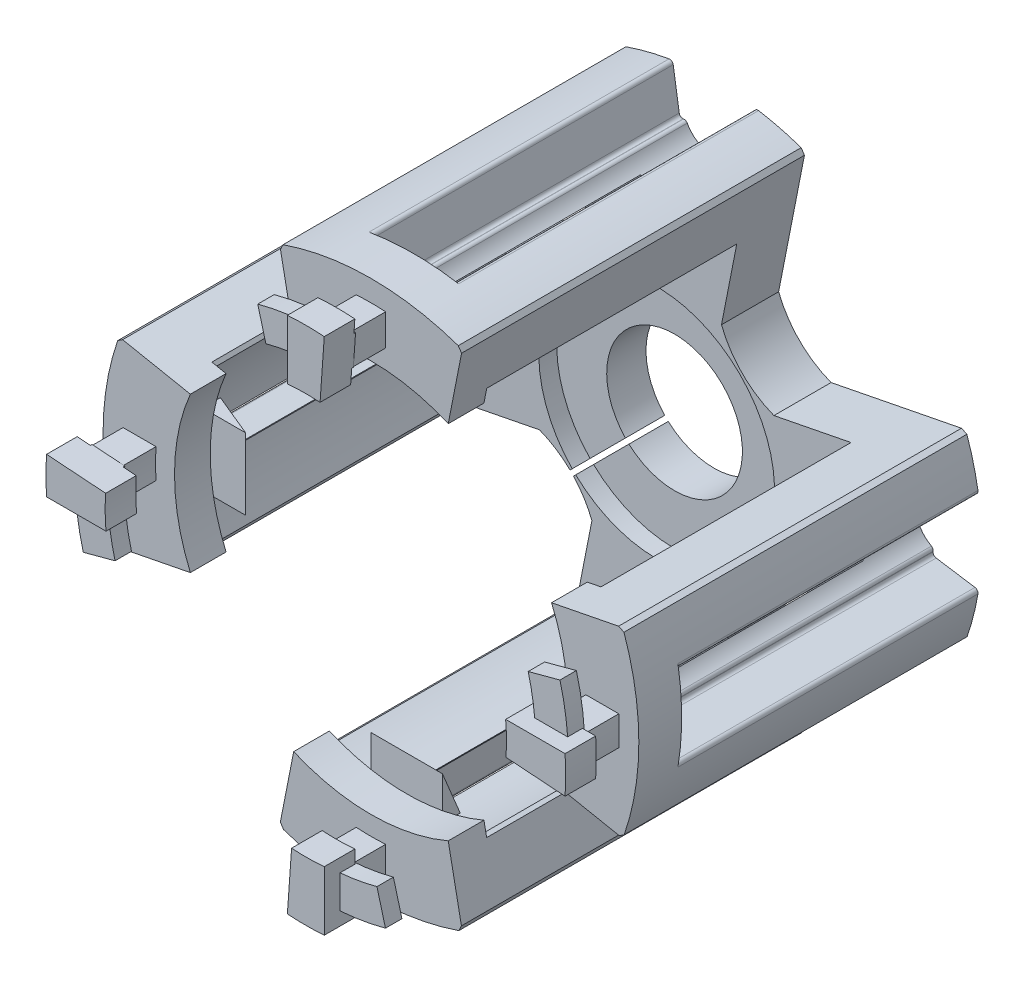
SolidWorks part; units mm, degrees
ref_plane "Front Plane" through (0, 0, 0) normal (0, 0, 1) x (1, 0, 0)
ref_plane "Top Plane" through (0, 0, 0) normal (0, 1, 0) x (1, 0, 0)
ref_plane "Right Plane" through (0, 0, 0) normal (1, 0, 0) x (0, 0, -1)
sketch "Sketch1" plane through (0, 0, 0) normal (0, 1, 0) x (1, 0, 0)
  line L2 (37.5, -48) -> (0, -48)
  line L3 (0, -48) -> (0, -45.5)
  line L4 (11.5, -43) -> (13, -43)
  line L5 (13, -43) -> (13, -45.5)
  line L6 (13, -45.5) -> (16.5, -45.5)
  line L7 (29, -43) -> (29, -8)
  line L11 (0, -5.5) -> (0, 0)
  line L12 (16.5, -5.5) -> (16.5, -8)
  line L13 (16.5, -8) -> (29, -8)
  line L14 (16.5, -45.5) -> (16.5, -43)
  line L15 (16.5, -43) -> (29, -43)
  line L18 (11.5, -43) -> (11.5, -45.5)
  line L19 (11.5, -45.5) -> (0, -45.5)
  line L23 (0, -5.5) -> (16.5, -5.5)
  line L26 (0, 0) -> (37.5, 0)
  line L28 (37.5, 0) -> (37.5, -48)
  dimension "D1" = 29
  dimension "D2" = 48
  dimension "D3" = 5.5
  dimension "D4" = 37.5
  dimension "D5" = 2.5
  dimension "D7" = 16.5
  dimension "D8" = 2.5
  dimension "D9" = 5
revolve "Revolve1" add sketch "Sketch1" angle 360 about L3 region at (18.75, 0, 47.3909)
sketch "Sketch13" plane through (0, 0, 48) normal (0, 0, 1) x (1, 0, 0)
  line L2 (0, 27.5) -> (0, 37.5) construction
  circle A0 centre (0, 0) radius 27.5 construction
  circle A1 centre (0, 0) radius 37.5 construction
  circle A3 centre (0, -32.5) radius 1.7
  circle A4 centre (0, 0) radius 32.5 construction
  circle A5 centre (-32.5, 0) radius 1.7
  circle A6 centre (0, 32.5) radius 1.7
  circle A7 centre (32.5, 0) radius 1.7
  point P15 (0, 32.5)
  dimension "D3" = 3.4
  dimension "D4" = 3.4
  dimension "D1" = 3.4
  dimension "D2" = 3.4
  dimension "D5" = 65
  dimension "D6" = 55
extrude "Cut-Extrude2" cut sketch "Sketch13" against normal through all
sketch "Sketch15" plane through (0, 0, 48) normal (0, 0, 1) x (1, 0, 0)
  circle A0 centre (32.5, 0) radius 3.25
  circle A1 centre (0, 32.5) radius 3.25
  circle A2 centre (0, 32.5) radius 1.7 construction
  circle A4 centre (32.5, 0) radius 1.7 construction
  circle A5 centre (-32.5, 0) radius 3.25
  dimension "D1" = 6.5
  dimension "D2" = 0
  dimension "D3" = 6.5
extrude "Cut-Extrude3" cut sketch "Sketch15" against normal through all from offset 6 offset against normal yes
sketch "Sketch19" plane through (0, 0, 0) normal (0, 0, 1) x (1, 0, 0)
  line L0 (0, 0) -> (-37.6803, 0) construction
  line L1 (0, 0) -> (-15.2028, 15.2028) construction
  line L2 (0, 0) -> (18.7383, 18.7383) construction
  line L3 (0, 16) -> (0, 21.5) construction
  line L4 (-16.41, 9.0705) -> (-25.2831, 10.8173)
  line L5 (-9.0705, 16.41) -> (-10.8173, 25.2831)
  line L6 (9.0705, 16.41) -> (10.8173, 25.2831)
  line L7 (16.41, 9.0705) -> (25.2831, 10.8173)
  line L8 (10.8173, 25.2831) -> (12.7804, 35.255)
  line L9 (25.2831, 10.8173) -> (35.255, 12.7804)
  line L10 (-10.8173, 25.2831) -> (-13.457, 38.6919)
  line L11 (-25.2831, 10.8173) -> (-41.6952, 14.0482)
  circle A0 centre (0, 0) radius 21.5 construction
  circle A1 centre (0, 0) radius 16 construction
  circle A5 centre (0, 0) radius 18.75 construction
  arc A7 (-12.7804, 35.255) -> (-35.255, 12.7804) centre (0, 0) ccw
  arc A9 (35.255, 12.7804) -> (12.7804, 35.255) centre (0, 0) ccw
  arc A12 (-16.41, 9.0705) -> (-9.0705, 16.41) centre (-21.0477, 21.0477) ccw
  arc A16 (16.41, 9.0705) -> (9.0705, 16.41) centre (21.0343, 21.0343) cw
  dimension "D1" = 32
  dimension "D2" = 43
  dimension "D5" = 12.8437
  dimension "D7" = 18.0174
  dimension "D8" = 37.5
  dimension "D6" = 12.8264
  dimension "D15" = 67.726
  dimension "D17" = 22.274
  dimension "D19" = 18.75
  dimension "D20" = 21.6346
  dimension "D22" = 45
  dimension "D23" = 37.5
  dimension "D3" = 8.8731
  dimension "D4" = 8.8731
  dimension "D9" = 8.8731
  dimension "D10" = 8.8731
  dimension "D11" = 25.2831
  dimension "D12" = 10.8173
  dimension "D13" = 18.75
  dimension "D14" = 18.75
  dimension "D16" = 67.726
  dimension "D18" = 21.5
  dimension "D21" = 50.5663
  dimension "D24" = 16.41
  dimension "D25" = 25.2831
extrude "Cut-Extrude7" cut sketch "Sketch19" along normal through all contours L4 | L4 | L5 | L5 | L6 | L6 | L7 | L7 region at (-20.2326, 20.2326, 0) region at (20.2324, 20.2324, 0)
sketch "Sketch22" plane through (0, 0, 0) normal (0, 0, 1) x (1, 0, 0)
  line L0 (0, 11.5) -> (0, -12.9413) construction
  circle A2 centre (0, 0) radius 9.5
  dimension "D4" = 19
extrude "Cut-Extrude9" cut sketch "Sketch22" along normal up to surface (8 mm away) up to face at (-0.0001, 10.9138, 8)
ref_plane "Plano1" through (0, 0, 25) normal (0, 0, -1) x (-1, 0, 0)
mirror "Simetría1" about plane through (0, 0, 0) normal (0, 1, 0) of "Cut-Extrude3", "Cut-Extrude7", "Cut-Extrude2"
sketch "Croquis2" plane through (0, 0, 48) normal (0, 0, 1) x (1, 0, 0)
  line L0 (0, 0) -> (28.257, 0) construction
  line L14 (0, 0) -> (-30.3161, 0) construction
  arc A12 (27.5, 0) -> (-27.5, 0) centre (0, 0) ccw
  arc A15 (-27.5, 0) -> (27.5, 0) centre (0, 0) ccw
  dimension "D1" = 27.5
extrude "Cortar-Extruir2" cut sketch "Croquis2" against normal blind 5
chamfer "Chaflán1" distance 0.5 angle 45 16 edges at (11.1132, 26.7861, 25.5) (26.7861, 11.1132, 25.5) (26.7861, -11.1132, 25.5) (11.1132, -26.7861, 25.5) (-11.1132, -26.7861, 25.5) (-26.7861, -11.1132, 25.5) (-26.7861, 11.1132, 25.5) (-11.1132, 26.7861, 25.5) (-12.7804, -35.255, 24) (-35.255, -12.7804, 24) (-35.255, 12.7804, 24) (-12.7804, 35.255, 24) (12.7804, 35.255, 24) (35.255, 12.7804, 24) (35.255, -12.7804, 24) (12.7804, -35.255, 24) first distance on face at (10.9453, 25.9336, 24.75) first distance on face at (27.8931, 0, 25.5) first distance on face at (25.9336, -10.9453, 24.75) first distance on face at (0, -27.8931, 25.5) first distance on face at (-10.9453, -25.9336, 24.75) first distance on face at (-27.8931, 0, 25.5) first distance on face at (-25.9336, 10.9453, 24.75) first distance on face at (0, 27.8931, 25.5) first distance on face at (-36.3775, 0, 24) first distance on face at (0, 36.3775, 24) first distance on face at (36.3775, 0, 24) first distance on face at (0, -36.3775, 24)
ref_plane "Plano8" through (0, 0, 41) normal (0, 0, 1) x (1, 0, 0)
sketch "Croquis28" plane through (0, 0, 41) normal (0, 0, 1) x (1, 0, 0)
  line L1 (-5, 29.5) -> (-5, 22.5)
  line L2 (-5, 22.5) -> (5, 22.5)
  line L3 (-5, -29.5) -> (-5, -22.5)
  line L4 (-5, -22.5) -> (5, -22.5)
  line L6 (0, -29.5) -> (5, -29.5)
  line L7 (0, -29.5) -> (-5, -29.5)
  line L8 (0, 29.5) -> (5, 29.5)
  line L9 (0, 29.5) -> (-5, 29.5)
  line L10 (5, 29.5) -> (5, 22.5)
  line L12 (5, -22.5) -> (5, -29.5)
  line L18 (-29.5, 0) -> (-29.5, 5)
  line L19 (-29.5, 5) -> (-22.5, 5)
  line L20 (-22.5, 5) -> (-22.5, -5)
  line L21 (-22.5, -5) -> (-29.5, -5)
  line L22 (-29.5, -5) -> (-29.5, 0)
  line L23 (29.5, 0) -> (29.5, 5)
  line L24 (29.5, 5) -> (22.5, 5)
  line L25 (22.5, 5) -> (22.5, -5)
  line L26 (22.5, -5) -> (29.5, -5)
  line L27 (29.5, -5) -> (29.5, 0)
  circle A2 centre (32.5, 0) radius 1.7 construction
  circle A3 centre (-32.5, 0) radius 1.7 construction
  circle A4 centre (0, 32.5) radius 1.7 construction
  circle A5 centre (0, -32.5) radius 1.7 construction
  dimension "D7" = 5
  dimension "D4" = 5
  dimension "D14" = 3
  dimension "D16" = 3
  dimension "D1" = 5
  dimension "D2" = 5
  dimension "D3" = 7
  dimension "D5" = 5
  dimension "D6" = 7
  dimension "D8" = 5
  dimension "D9" = 7
  dimension "D10" = 5
  dimension "D11" = 5
  dimension "D12" = 7
  dimension "D13" = 3
  dimension "D15" = 3
extrude "Saliente-Extruir4" add sketch "Croquis28" along normal up to surface (2 mm away) and the other way blind 4 contours L21 L22 L18 L19 L20 | L6 L12 L4 L3 L7 | L27 L23 L24 L25 L26 | L8 L10 L2 L1 L9 up to face at (27.2039, -0.0149, 43)
sketch "Croquis1" plane through (0, 0, 25) normal (0, 0, -1) x (-1, 0, 0)
  line L0 (4.7692, 30.6309) -> (5.7692, 37.0536)
  line L1 (-4.7692, 30.6309) -> (-5.7692, 37.0536)
  line L8 (-37.0536, 5.7692) -> (-30.6309, 4.7692)
  line L9 (-37.0536, -5.7692) -> (-30.6309, -4.7692)
  line L10 (-5.7692, -37.0536) -> (-4.7692, -30.6309)
  line L11 (4.7692, -30.6309) -> (5.7692, -37.0536)
  line L12 (30.6309, -4.7692) -> (37.0536, -5.7692)
  line L13 (30.6309, 4.7692) -> (37.0536, 5.7692)
  circle A0 centre (32.5, 0) radius 3.25 construction
  circle A1 centre (0, -32.5) radius 1.7 construction
  circle A2 centre (0, 32.5) radius 1.7 construction
  arc A10 (-37.0536, 5.7692) -> (-37.0536, -5.7692) centre (0, 0) ccw
  arc A14 (37.0536, -5.7692) -> (37.0536, 5.7692) centre (0, 0) ccw
  arc A16 (30.6309, -4.7692) -> (30.6309, 4.7692) centre (0, 0) ccw
  arc A17 (4.7692, 30.6309) -> (-4.7692, 30.6309) centre (0, 0) ccw
  arc A18 (5.7692, 37.0536) -> (-5.7692, 37.0536) centre (0, 0) ccw
  circle A19 centre (0, -32.5) radius 1.7 construction
  arc A20 (-4.7692, -30.6309) -> (4.7692, -30.6309) centre (0, 0) ccw
  arc A21 (-5.7692, -37.0536) -> (5.7692, -37.0536) centre (0, 0) ccw
  arc A22 (-30.6309, 4.7692) -> (-30.6309, -4.7692) centre (0, 0) ccw
  dimension "D4" = 5
  dimension "D6" = 17.7
  dimension "D9" = 31
  dimension "D2" = 37.5
  dimension "D3" = 5
  dimension "D5" = 5
  dimension "D13" = 5
  dimension "D19" = 72.3
  dimension "D15" = 31
  dimension "D17" = 37.5
  dimension "D20" = 37.5
  dimension "D7" = 5.7692
  dimension "D8" = 5
  dimension "D10" = 9.5385
  dimension "D11" = 6.4226
  dimension "D12" = 9.5385
  dimension "D14" = 72.3
  dimension "D16" = 72.3
  dimension "D18" = 17.7
  dimension "D21" = 5
extrude "Cortar-Extruir10" cut sketch "Croquis1" against normal up to surface and the other way up to surface up to face at (1.7, 32.5, 42) other way up to face at (35.75, 0, 0)
ref_plane "Plano9" through (0, 0, 25) normal (0, 0, 1) x (1, 0, 0)
sketch "Croquis29" plane through (0, 0, 0) normal (0, 0, 1) x (1, 0, 0)
  circle A1 centre (0, -32.5) radius 4.25
  circle A2 centre (0, 32.5) radius 4.25
  circle A3 centre (32.5, 0) radius 4.25
  circle A5 centre (-32.5, 0) radius 4.25
  dimension "D1" = 8.5
  dimension "D2" = 8.5
  dimension "D3" = 8.5
  dimension "D4" = 8.5
extrude "Cortar-Extruir11" cut sketch "Croquis29" along normal up to surface (42 mm away) up to face at (1.7, -32.5, 42)
fillet "Redondeo2" radius 0.5 24 edges at (-37.0536, -5.7692, 21) (-30.6309, -4.7692, 21) (-37.0536, 5.7692, 21) (-30.6309, 4.7692, 21) (-5.7692, 37.0536, 21) (-4.7692, 30.6309, 21) (5.7692, 37.0536, 21) (4.7692, 30.6309, 21) (37.0536, 5.7692, 21) (30.6309, 4.7692, 21) (30.6309, -4.7692, 21) (37.0536, -5.7692, 21) (5.7692, -37.0536, 21) (-5.7692, -37.0536, 21) (-4.7692, -30.6309, 21) (4.7692, -30.6309, 21) (-3.876, -30.7567, 21) (3.876, -30.7567, 21) (-30.7567, 3.876, 21) (-30.7567, -3.876, 21) (-3.876, 30.7567, 21) (3.876, 30.7567, 21) (30.7567, 3.876, 21) (30.7567, -3.876, 21)
sketch "Croquis35" plane through (0, 0, 0) normal (0, 1, 0) x (1, 0, 0)
  line L0 (-28.5254, -37) -> (-22.5, -37)
  line L1 (-28.5254, -37) -> (-28.5254, -40.52)
  line L2 (-28.5254, -40.52) -> (-22.5, -43.0195)
  line L3 (-22.5, -37) -> (-22.5, -43.0195)
  line L5 (-26.9754, -43) -> (-26.9754, -8) construction
  dimension "D1" = 1.55
  dimension "D2" = 3.52
  dimension "D3" = 112.53
extrude "Cortar-Extruir14" cut sketch "Croquis35" against normal up to surface and the other way up to surface up to face at (-25.8346, -5, 40.6) other way up to face at (-25.8346, 5, 40.6)
mirror "Simetría2" about plane through (0, 0, 0) normal (1, 0, 0) of "Cortar-Extruir14"
sketch "Croquis37" plane through (0, 0, 0) normal (1, 0, 0) x (0, 0, -1)
  line L1 (-40.5234, -28.5254) -> (-43.0234, -22.5)
  line L2 (-43.0234, -22.5) -> (-35.0234, -22.5)
  line L3 (-43, -26.9754) -> (-8, -26.9754) construction
  line L4 (-40.5234, -28.5254) -> (-35.0234, -28.5254)
  line L5 (-35.0234, -28.5254) -> (-35.0234, -22.5)
  dimension "D1" = 6.0254
  dimension "D2" = 1.55
  dimension "D3" = 8
  dimension "D4" = 112.534
  dimension "D5" = 35.0234
extrude "Cortar-Extruir15" cut sketch "Croquis37" along normal up to surface and the other way up to surface up to face at (5, -25.8346, 40.6) other way up to face at (-5, -25.8346, 40.6)
mirror "Simetría3" about plane through (0, 0, 0) normal (0, 1, 0) of "Cortar-Extruir15"
ref_plane "Plano10" through (0, 0, 38) normal (0, 0, 1) x (1, 0, 0)
sketch "Croquis40" plane through (0, 0, 38) normal (0, 0, 1) x (1, 0, 0)
  circle A0 centre (0, 0) radius 29
  dimension "D1" = 58
extrude "Cortar-Extruir17" cut sketch "Croquis40" against normal blind 2 and the other way up to vertex (2.5234 mm away) other way up to point (-1.505, -28.5254, 40.5234)
sketch "Croquis41" plane through (0, 0, 0) normal (1, 0, 0) x (0, 0, -1)
  line L0 (0, 0) -> (-71.6784, 0) construction
scale "Scale1" scale about centroid uniform scaling yes scale factor 2.171429
sketch "Sketch26" plane through (0, 0, -22.705) normal (0, 0, -1) x (-1, 0, 0)
  line L0 (-0.7071, -0.7071) -> (0.3536, 0.3536)
  line L1 (0, 0) -> (0, 74.1003)
  line L2 (42.6836, -44.0978) -> (43.7442, -43.0371)
  line L3 (0, 0) -> (-58.3903, 0)
  line L6 (0.3536, 0.3536) -> (43.7442, -43.0371)
  line L7 (-0.7071, -0.7071) -> (42.6836, -44.0978)
extrude "Cut-Extrude10" cut sketch "Sketch26" against normal blind 23 contours L6 | L7 L6 | L7 region at (-21.5186, -21.8721, -22.705)
sketch "Sketch27" plane through (0, 0, 68.495) normal (0, 0, -1) x (-1, 0, 0)
  circle A0 centre (-70.5715, 0) radius 4.5909
  circle A1 centre (0, -70.5031) radius 4.507
  circle A2 centre (70.5714, 0) radius 5.5728
  circle A3 centre (-0.0001, 70.5714) radius 4.5465
extrude "Boss-Extrude1" add sketch "Sketch27" against normal up to surface (13.0286 mm away) up to face at (3.6915, 70.5714, 81.5236)
sketch "Sketch28" plane through (0, 0, 81.5236) normal (0, 0, 1) x (1, 0, 0)
  line L0 (0, 65.3262) -> (0, 65.4789)
  line L1 (-4.4688, 75.4789) -> (4.4688, 75.4789)
  line L3 (4.4688, 75.4789) -> (4.4688, 65.3262)
  line L4 (4.4688, 65.3262) -> (-4.4688, 65.3262)
  line L5 (-4.4688, 75.4789) -> (-4.4688, 65.3262)
  circle A1 centre (0, 0) radius 75.4789
  circle A2 centre (0, 0) radius 65.4789
extrude "Boss-Extrude2" add sketch "Sketch28" along normal blind 10 contours A2 L3 A1 L5 region at (0, 70.4314, 81.5236)
sketch "Sketch29" plane through (0, 0, 91.5236) normal (0, 0, 1) x (1, 0, 0)
  line L0 (0, 65) -> (0, 75)
  line L1 (0, 75) -> (0, 65)
  line L2 (-16.8232, 62.7852) -> (-19.4114, 72.4444)
  line L3 (16.8232, 62.7852) -> (19.4114, 72.4444)
  arc A0 (19.4114, 72.4444) -> (-19.4114, 72.4444) centre (0, 0) ccw
  arc A1 (16.8232, 62.7852) -> (-16.8232, 62.7852) centre (0, 0) ccw
  arc M6 (-4.4688, 65.3262) -> (4.4688, 65.3262) centre (0, 0) cw
  line M7 (4.4688, 65.3262) -> (4.4688, 75.3465)
  line M9 (-4.4688, 75.3465) -> (-4.4688, 65.3262)
  dimension "D1" = 15
extrude "Boss-Extrude3" add sketch "Sketch29" along normal blind 5 contours A1 L0 A0 L2 M6 M9 | L0 A0 M9 M6 | A0 L0 M7 M6 | A1 L3 A0 L0 M7 M6 region at (-11.2118, 69.0572, 91.5236) region at (11.2118, 69.0572, 91.5236) region at (-2.2351, 70.1918, 91.5236) region at (2.2351, 70.1918, 91.5236)
sketch "Sketch30" plane through (0, 0, 96.5236) normal (0, 0, 1) x (1, 0, 0)
  line L0 (0.0001, 59.7143) -> (0.0001, 59.7454)
  line L1 (0.0001, 81.2354) -> (0.0001, 81.4286)
  line L2 (5.6055, 59.7454) -> (-5.6054, 59.7454)
  line L3 (5.6055, 59.7454) -> (5.6055, 81.2354)
  line L4 (5.6055, 81.2354) -> (-5.6054, 81.2354)
  line L5 (-5.6054, 59.7454) -> (-5.6054, 81.2354)
  arc A0 (5.6055, 81.2354) -> (-5.6054, 81.2354) centre (0.0001, 0) ccw
  point P6 (0.0001, 70.4904)
  arc M6 (19.4114, 72.4444) -> (-19.4114, 72.4444) centre (0, 0) ccw
  arc M8 (-16.8232, 62.7852) -> (16.8232, 62.7852) centre (0, 0) cw
extrude "Boss-Extrude4" add sketch "Sketch30" along normal blind 4.8 and the other way blind 4.5 contours L5 L3 L4 M6 | L5 L3 M8 M6 | L5 L2 L3 M8 region at (0.0001, 78.0824, 96.5236) region at (0.0001, 69.9247, 96.5236) region at (0.0001, 62.3329, 96.5236)
sketch "Sketch31" plane through (0, 0, 91.5236) normal (0, 0, -1) x (-1, 0, 0)
  circle A0 centre (0, 0) radius 65
  circle A1 centre (0, 0) radius 75
  circle A2 centre (0, 0) radius 89.1867
  arc M2 (-4.4688, 74.8667) -> (-19.4114, 72.4444) centre (0, 0) ccw
  arc M4 (-16.8232, 62.7852) -> (16.8232, 62.7852) centre (0, 0) cw
  arc M6 (19.4114, 72.4444) -> (4.4688, 74.8667) centre (0, 0) ccw
extrude "Cut-Extrude12" cut sketch "Sketch31" along direction (0, 0, -1) on the side of the normal blind 10 contours A0 M4 | A2 A1 M6 M2 region at (0, 0, 91.5236) region at (86.6641, 0, 91.5236)
sketch "Sketch32" plane through (0, 0, 101.3236) normal (0, 0, 1) x (1, 0, 0)
  circle A0 centre (0.0001, 0) radius 61
  circle A1 centre (0.0001, 0) radius 79
  circle A2 centre (0.0001, 0) radius 50.7725
  circle A3 centre (0.0001, 0) radius 92.1535
  line M1 (-5.6054, 81.2354) -> (-5.6054, 59.7454)
  line M2 (-5.6054, 59.7454) -> (5.6055, 59.7454)
  line M3 (5.6055, 59.7454) -> (5.6055, 81.2354)
  line M4 (5.6055, 81.2354) -> (-5.6054, 81.2354)
extrude "Cut-Extrude15" cut sketch "Sketch32" against normal blind 10 contours A1 M3 M4 M1 | A0 M3 M1 M2 region at (0.0001, 60.3322, 101.3236) region at (0.0001, 80.0838, 101.3236)
sketch "Sketch33" plane through (0, 0, 96.5236) normal (0, 0, 1) x (1, 0, 0)
  line L2 (5.6055, 74.7902) -> (5.6055, 64.7578)
  line L3 (16.8232, 62.7852) -> (19.4114, 72.4444)
  line L4 (5.6055, 74.7902) -> (5.6055, 64.7578)
  line L5 (16.8232, 62.7852) -> (19.4114, 72.4444)
  arc A2 (16.8232, 62.7852) -> (5.6055, 64.7578) centre (0, 0) ccw
  arc A3 (19.4114, 72.4444) -> (5.6055, 74.7902) centre (0, 0) ccw
  arc A4 (16.8232, 62.7852) -> (5.6055, 64.7578) centre (0, 0) ccw
  arc A5 (19.4114, 72.4444) -> (5.6055, 74.7902) centre (0, 0) ccw
  dimension "D1" = 0
extrude "Cut-Extrude16" cut sketch "Sketch33" against normal blind 10
sketch "Sketch34" plane through (0, 0, 101.3236) normal (0, 0, 1) x (1, 0, 0)
  line L0 (4.3283, 60.8463) -> (5.6055, 78.8009)
  line L3 (5.6055, 60.7419) -> (5.6055, 78.8009) construction
  line L4 (5.6055, 60.7419) -> (5.6055, 78.8009)
  arc A1 (5.6055, 60.7419) -> (-5.6054, 60.7419) centre (0.0001, 0) ccw construction
  arc A2 (5.6055, 60.7419) -> (4.3283, 60.8463) centre (0.0001, 0) ccw
extrude "Cut-Extrude17" cut sketch "Sketch34" against normal blind 15
sketch "Sketch35" plane through (0, 0, 91.5236) normal (0, 0, -1) x (-1, 0, 0)
  circle A0 centre (0, 0) radius 65.4789
extrude "Cut-Extrude18" cut sketch "Sketch35" against normal up to surface (0.5 mm away) up to face at (-0.5685, 62.8965, 92.0236)
sketch "Sketch36" plane through (0, 0, 92.0236) normal (0, 0, -1) x (-1, 0, 0)
  line L0 (15.7224, 58.6769) -> (16.9472, 63.2478)
  line L1 (5.6054, 60.7419) -> (5.6054, 65.2385)
  line L2 (5.6054, 60.7419) -> (15.7224, 58.6769)
  arc A0 (16.9472, 63.2478) -> (5.6054, 65.2385) centre (0, 0) ccw
extrude "Cut-Extrude19" cut sketch "Sketch36" against normal blind 11
pattern_circular "CirPattern1" count 4 over 360 about axis through (0, 0, 0) along (0, 0, 1) of "Boss-Extrude3", "Boss-Extrude4", "Cut-Extrude15", "Boss-Extrude2", "Cut-Extrude17" reverse direction yes
sketch "Sketch37" plane through (0, 0, 101.3236) normal (0, 0, 1) x (1, 0, 0)
  line L0 (74.7647, -5.4682) -> (46.8408, -4.7529)
  line L1 (46.8408, -4.7529) -> (48.9149, -17.6123)
  line L2 (48.9149, -17.6123) -> (80.4411, -22.8667)
  line L3 (80.4411, -22.8667) -> (75.1872, -5.4682)
  line L4 (75.1872, -5.4682) -> (74.7647, -5.4682)
  line L5 (-5.5218, -74.9544) -> (-5.1689, -61.1781)
  line L6 (-5.1689, -61.1781) -> (-17.9927, -61.1781)
  line L7 (-17.9927, -61.1781) -> (-22.9754, -78.12)
  line L8 (-22.9754, -78.12) -> (-5.5218, -74.9544)
  line L9 (-74.8242, 5.4684) -> (-60.3397, 5.4684)
  line L10 (-60.3397, 5.4684) -> (-59.9574, 20.3939)
  line L11 (-59.9574, 20.3939) -> (-77.5565, 21.2261)
  line L12 (-77.5565, 21.2261) -> (-74.8242, 5.4684)
  arc A0 (-26.5394, -76.9823) -> (26.7353, -76.9145) centre (0.0001, 0) ccw construction
extrude "Cut-Extrude20" cut sketch "Sketch37" against normal blind 11
